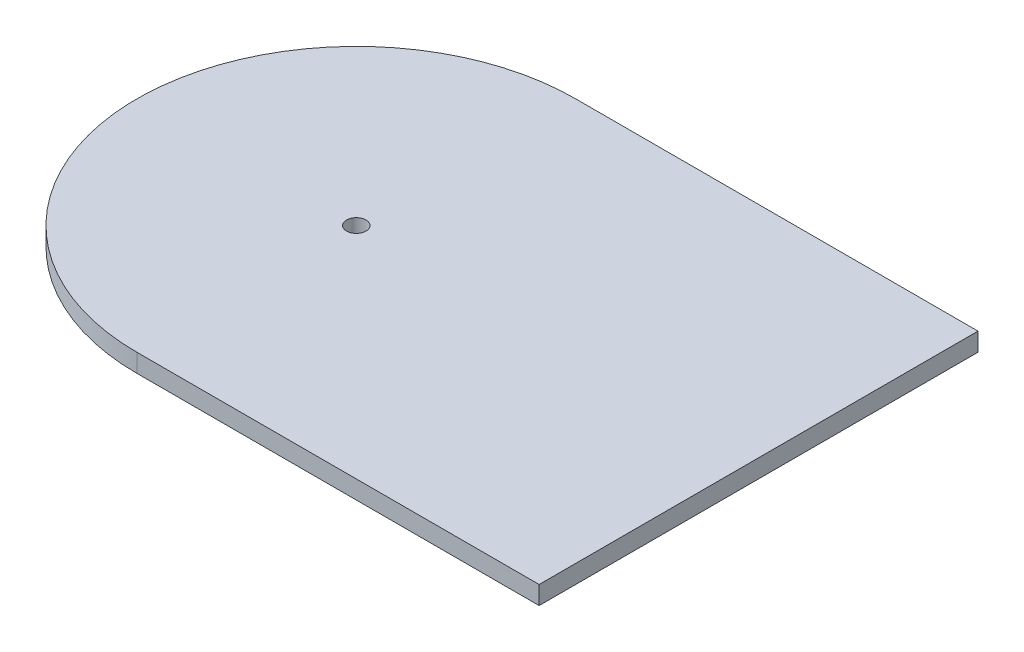
SolidWorks part; units mm, degrees
ref_plane "Front Plane" through (0, 0, 0) normal (0, 0, 1) x (1, 0, 0)
ref_plane "Top Plane" through (0, 0, 0) normal (0, 1, 0) x (1, 0, 0)
ref_plane "Right Plane" through (0, 0, 0) normal (1, 0, 0) x (0, 0, -1)
sketch "Sketch1" plane through (0, 0, 0) normal (0, 1, 0) x (1, 0, 0)
  line L0 (0, -76.2) -> (0, 76.2)
  line L1 (0, -76.2) -> (139.7, -76.2)
  line L2 (0, 76.2) -> (139.7, 76.2)
  line L3 (139.7, -76.2) -> (139.7, 76.2)
  circle A0 centre (0, 0) radius 76.2
  circle A1 centre (0, 0) radius 3.3655
  dimension "D1" = 152.4
  dimension "D2" = 6.731
  dimension "D3" = 139.7
extrude "Boss-Extrude1" add sketch "Sketch1" along normal blind 6.35 contours A1 L0 A0 | A1 L0 A0 | A0 L1 L3 L2 region at (-32.4007, 0, 0) region at (97.9625, 0, 0) region at (32.4007, 0, 0)
